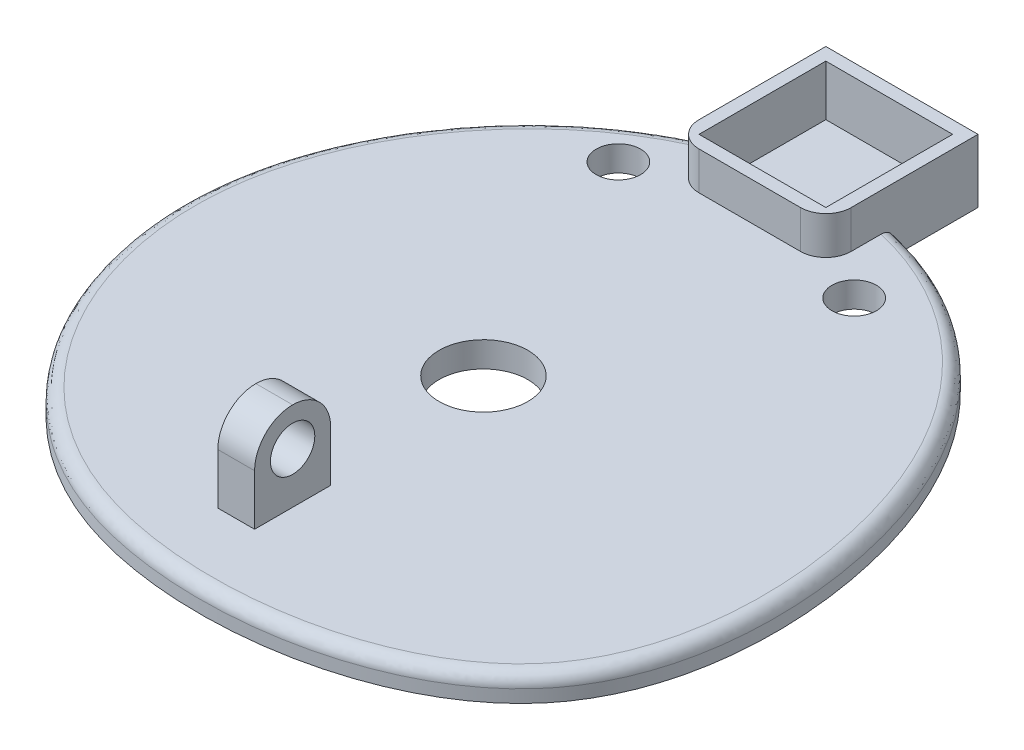
SolidWorks part; units mm, degrees
other "Markup1"
sketch "Sketch52"
ref_plane "Front Plane" through (0, 0, 0) normal (0, 0, 1) x (1, 0, 0)
ref_plane "Top Plane" through (0, 0, 0) normal (0, 1, 0) x (1, 0, 0)
ref_plane "Right Plane" through (0, 0, 0) normal (1, 0, 0) x (0, 0, -1)
sketch "Sketch1" plane through (0, 0, 0) normal (0, -1, 0) x (1, 0, 0)
  spline S0 degree 3 poles (-31.2554, -3.659) (-3.865, -36.4974) (28.4311, -18.0096) (27.0731, 23.7911) (-13.0922, 29.3353) (-31.2554, -3.659) (-3.865, -36.4974) (28.4311, -18.0096) knots -0.582232 -0.423204 -0.235785 0 0.296836 0.417768 0.576796 0.764215 1 1.296836 1.417768 1.576796 only from (-5, -26) to (-5, -26)
  point P0 (26.2046, -3.7151)
  dimension "D1" = 24
  dimension "D3" = 5
  dimension "D5" = 26
extrude "Boss-Extrude1" add sketch "Sketch1" against normal blind 2
sketch "Sketch53" plane through (0, 0, 0) normal (0, -1, 0) x (1, 0, 0)
  circle A0 centre (0, 0) radius 3.5
  dimension "D1" = 7
extrude "Cut-Extrude1" cut sketch "Sketch53" against normal through all
sketch "Sketch54" plane through (0, 2, 0) normal (0, 1, 0) x (1, 0, 0)
  line L0 (0, 33.4854) -> (0, -33.4854) construction
  line L1 (0, 0) -> (21130.9131, 45315.3894) construction
  circle A0 centre (9.2976, 19.9388) radius 1.75
  circle A2 centre (-9.2976, 19.9388) radius 1.75
  point P7 (0, 0)
  dimension "D3" = 3.5
  dimension "D1" = 22
  dimension "D2" = 25
extrude "Cut-Extrude2" cut sketch "Sketch54" against normal up to next
sketch "Sketch58" plane through (0, 2, 0) normal (0, 1, 0) x (1, 0, 0)
  line L1 (-1.45, -13.5) -> (1.45, -13.5)
  line L2 (-1.45, -13.5) -> (-1.45, -19.5)
  line L3 (-1.45, -19.5) -> (1.45, -19.5)
  line L4 (1.45, -13.5) -> (1.45, -19.5)
  line L5 (-1.45, -13.5) -> (1.45, -19.5) construction
  line L6 (-1.45, -19.5) -> (1.45, -13.5) construction
  point P0 (0, -16.5)
  dimension "D1" = 6
  dimension "D2" = 16.5
  dimension "D3" = 2.9
extrude "Boss-Extrude3" add sketch "Sketch58" along normal blind 7
sketch "Sketch59" plane through (1.45, 0, 0) normal (1, 0, 0) x (0, 0, -1)
  line L0 (-19.5, 2) -> (-13.5, 2) construction
  circle A0 centre (-16.5, 6) radius 1.75
  point P5 (-16.5, 2)
  dimension "D2" = 3.5
  dimension "D1" = 4
extrude "Cut-Extrude5" cut sketch "Sketch59" against normal up to next
fillet "Fillet2" radius 3 2 edges at (0, 9, 13.5) (0, 9, 19.5)
sketch "Sketch62" plane through (0, 0, 0) normal (0, 1, 0) x (1, 0, 0)
  line L1 (-6, 21) -> (6, 21)
  line L2 (-6, 21) -> (-6, 33)
  line L3 (-6, 33) -> (6, 33)
  line L4 (6, 21) -> (6, 33)
  line L5 (-6, 21) -> (6, 33) construction
  line L6 (-6, 33) -> (6, 21) construction
  point P0 (0, 27)
  point P5 (0, 0)
  dimension "D1" = 27
  dimension "D2" = 12
extrude "Boss-Extrude5" add sketch "Sketch62" along normal blind 5
sketch "Sketch63" plane through (0, 5, 0) normal (0, 1, 0) x (1, 0, 0)
  line L0 (6, 21) -> (6, 33) construction
  line L1 (-5, 22) -> (5, 22)
  line L2 (-5, 22) -> (-5, 32)
  line L3 (-5, 32) -> (5, 32)
  line L4 (5, 22) -> (5, 32)
  line L5 (-5, 22) -> (5, 32) construction
  line L6 (-5, 32) -> (5, 22) construction
  point P0 (0, 27)
  point P5 (0, 0)
  point P7 (0, 0)
  point P10 (6, 27)
  dimension "D1" = 10
extrude "Cut-Extrude6" cut sketch "Sketch63" against normal blind 4
fillet "Fillet4" radius 2 2 edges at (6, 3.5, -21) (-6, 3.5, -21)
fillet "Fillet5" radius 1 1 edges
